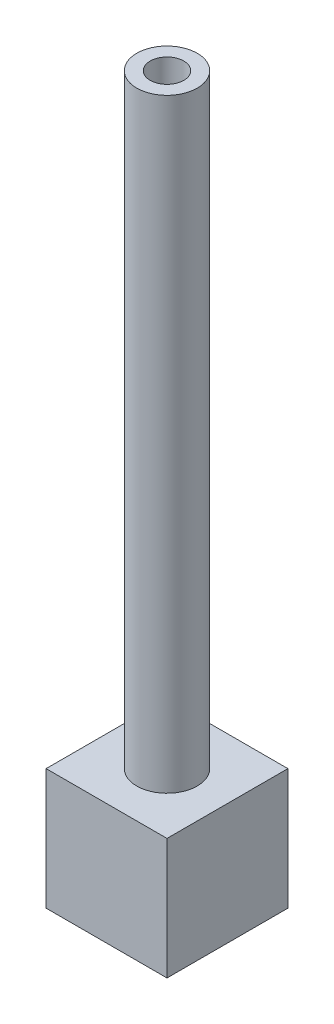
SolidWorks part; units mm, degrees
ref_plane "Front Plane" through (0, 0, 0) normal (0, 0, 1) x (1, 0, 0)
ref_plane "Top Plane" through (0, 0, 0) normal (0, 1, 0) x (1, 0, 0)
ref_plane "Right Plane" through (0, 0, 0) normal (1, 0, 0) x (0, 0, -1)
sketch "Sketch1" plane through (0, 0, 0) normal (0, 1, 0) x (1, 0, 0)
  circle A0 centre (0, 0) radius 2.78
  circle A1 centre (0, 0) radius 5
  dimension "D1" = 5.56
  dimension "D2" = 10
extrude "Boss-Extrude1" add sketch "Sketch1" along normal blind 100
sketch "Sketch2" plane through (0, 0, 0) normal (0, -1, 0) x (1, 0, 0)
  line L1 (10, -10) -> (-10, -10)
  line L2 (10, -10) -> (10, 10)
  line L3 (10, 10) -> (-10, 10)
  line L4 (-10, -10) -> (-10, 10)
  line L5 (10, -10) -> (-10, 10) construction
  line L6 (10, 10) -> (-10, -10) construction
  point P0 (0, 0)
  dimension "D1" = 20
  dimension "D2" = 20
extrude "Boss-Extrude2" add sketch "Sketch2" along normal blind 20
ref_point "Point1"
ref_point "Point2"
ref_axis "BarrelRotationAxis" through (-10, -10, 0) along (1, 0, 0)
ref_plane "Plane3" through (0, 0, 0) normal (-1, 0, 0) x (0, 0, 1)
ref_point "BarrelOrigin"
